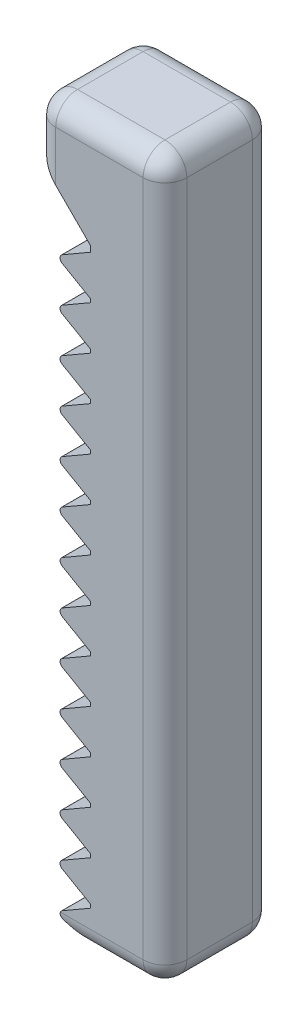
SolidWorks part; units mm, degrees
ref_plane "Front" through (0, 0, 0) normal (0, 0, 1) x (1, 0, 0)
ref_plane "Top" through (0, 0, 0) normal (0, 1, 0) x (1, 0, 0)
ref_plane "Right" through (0, 0, 0) normal (1, 0, 0) x (0, 0, -1)
sketch "Sketch1" plane through (0, 0, 0) normal (0, 1, 0) x (1, 0, 0)
  line L1 (-3, -2.5) -> (3, -2.5)
  line L2 (-3, -2.5) -> (-3, 2.5)
  line L3 (-3, 2.5) -> (3, 2.5)
  line L4 (3, -2.5) -> (3, 2.5)
  line L5 (-3, -2.5) -> (3, 2.5) construction
  line L6 (-3, 2.5) -> (3, -2.5) construction
  point P0 (0, 0)
  dimension "D1" = 5
  dimension "D2" = 6
extrude "Boss-Extrude1" add sketch "Sketch1" along normal blind 33
sketch "Sketch2" plane through (0, 0, -2.5) normal (0, 0, -1) x (-1, 0, 0)
  line L0 (3, 33) -> (3, 0) construction
  line L2 (3, 2.5) -> (3, 30.7)
  line L3 (3, 30.7) -> (0.4, 28.1)
  line L4 (0.4, 5.1) -> (0.4, 28.1)
  line L5 (3, 2.5) -> (0.4, 5.1) construction
  line L6 (-3, 0) -> (3, 0) construction
  line L7 (0.4, 5.1) -> (0.4, 0)
  line L8 (0.4, 0) -> (3, 0)
  line L9 (3, 0) -> (3, 2.5)
  dimension "D1" = 45
  dimension "D2" = 23
  dimension "D3" = 2.6
  dimension "D4" = 2.5
  dimension "D5" = 45
extrude "Cut-Extrude1" cut sketch "Sketch2" against normal through all both and the other way through all
sketch "Sketch3" plane through (0, 0, -2.5) normal (0, 0, -1) x (-1, 0, 0)
  line L0 (0.4, 0) -> (1.7, 0.7506)
  line L1 (1.7, 1.097) -> (0.4, 1.8475)
  line L2 (0.4, 0) -> (0.4, 28.1) construction
  line L3 (0.4, 1.8475) -> (0.4, 0)
  line L4 (1.7, 1.097) -> (2, 0.9238) construction
  line L5 (2, 0.9238) -> (1.7, 0.7506) construction
  line L6 (0.4, 0) -> (0.4, 28.1) construction
  line L7 (-3, 0) -> (0.4, 0) construction
  arc A0 (1.7, 0.7506) -> (1.7, 1.097) centre (1.6, 0.9238) ccw
  dimension "D1" = 0.2
  dimension "D2" = 60
  dimension "D3" = 1.6
extrude "Boss-Extrude2" add sketch "Sketch3" against normal up to surface (5 mm away) up to face at (-0.1333, 20.8, 2.5)
pattern_linear "LPattern1" count 14 spacing 2 along (0, 1, 0) of "Boss-Extrude2"
fillet "Fillet1" radius 1 13 edges at (1.3, 0, -2.5) (1.3, 0, 2.5) (-3, 33, 0) (-3, 31.85, 2.5) (-3, 30.7, 0) (-3, 31.85, -2.5) (3, 16.5, 2.5) (3, 33, 0) (3, 16.5, -2.5) (3, 0, 0) (0, 33, 2.5) (0, 33, -2.5) (-0.4, 0, 0)
